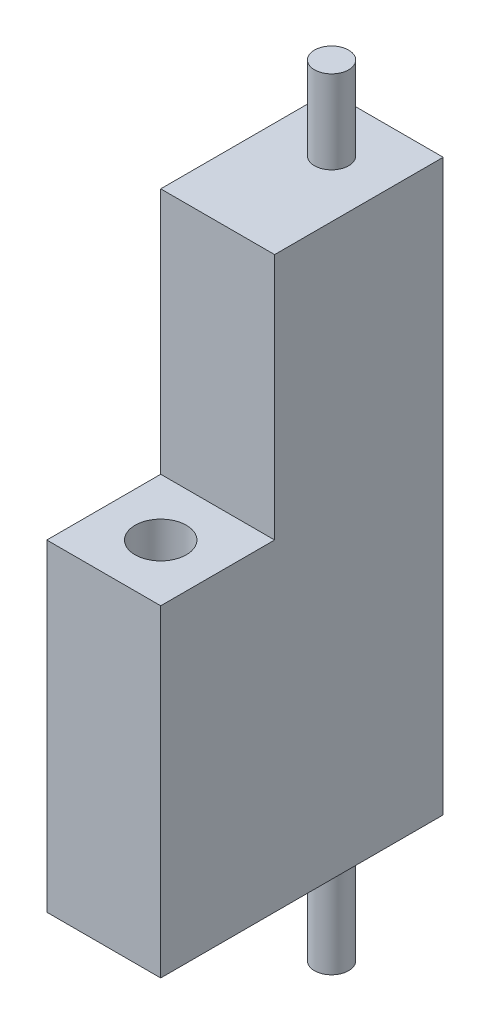
SolidWorks part; units mm, degrees
material "3003 合金"
ref_plane "前视基准面" through (0, 0, 0) normal (0, 0, 1) x (1, 0, 0)
ref_plane "上视基准面" through (0, 0, 0) normal (0, 1, 0) x (1, 0, 0)
ref_plane "右视基准面" through (0, 0, 0) normal (1, 0, 0) x (0, 0, -1)
sketch "草图1" plane through (0, 0, 0) normal (0, 0, 1) x (1, 0, 0)
  line L0 (22.5, 0) -> (22.5, 287.3668) construction
  line L1 (0, 0) -> (16.5, 0)
  line L2 (0, 0) -> (0, 10)
  line L3 (0, 10) -> (16.5, 10)
  line L4 (16.5, 0) -> (16.5, 10)
  line L5 (16.5, 0) -> (28.5, 0)
  line L6 (16.5, 0) -> (16.5, 10)
  line L7 (16.5, 10) -> (28.5, 10)
  line L8 (28.5, 0) -> (28.5, 10)
  line L9 (28.5, 10) -> (45, 10)
  line L10 (28.5, 10) -> (28.5, 0)
  line L11 (28.5, 0) -> (45, 0)
  line L12 (45, 10) -> (45, 0)
  line L13 (0, 10) -> (1, 10)
  line L14 (0, 10) -> (0, 102)
  line L15 (0, 102) -> (1, 102)
  line L16 (1, 10) -> (1, 102)
  line L17 (1, 102) -> (44, 102)
  line L18 (1, 102) -> (1, 10)
  line L19 (1, 10) -> (44, 10)
  line L20 (44, 102) -> (44, 10)
  line L21 (44, 102) -> (45, 102)
  line L22 (44, 102) -> (44, 10)
  line L23 (44, 10) -> (45, 10)
  line L24 (45, 102) -> (45, 10)
  line L25 (0, 0) -> (-10, 0)
  line L26 (0, 0) -> (0, 250)
  line L27 (0, 250) -> (-10, 250)
  line L28 (-10, 0) -> (-10, 250)
  line L29 (45, 0) -> (55, 0)
  line L30 (45, 0) -> (45, 250)
  line L31 (45, 250) -> (55, 250)
  line L32 (55, 0) -> (55, 250)
  line L33 (-10, 250) -> (55, 250)
  line L34 (-10, 250) -> (-10, 260)
  line L35 (-10, 260) -> (55, 260)
  line L36 (55, 260) -> (55, 250)
  line L37 (-10, 250) -> (55, 250)
  line L46 (-27.5, 0) -> (72.5, 0)
  line L47 (147.5, 475.7809) -> (197.5, 475.7809)
  line L52 (147.5, 475.7809) -> (172.5, 475.7809)
  line L56 (72.5, 0) -> (-27.5, 0)
  line L57 (72.5, 0) -> (72.5, 250)
  line L58 (72.5, 250) -> (-27.5, 250)
  line L59 (-27.5, 0) -> (-27.5, 250)
  line L60 (-27.5, 0) -> (72.5, 0)
  line L61 (-27.5, 0) -> (-27.5, -33)
  line L62 (-27.5, -33) -> (72.5, -33)
  line L63 (72.5, 250) -> (72.5, 0)
  line L64 (72.5, 0) -> (72.5, -33)
  point P21 (22.5, 0)
  dimension "D1" = 16.5
  dimension "D2" = 12
  dimension "D3" = 16.5
  dimension "D4" = 10
  dimension "D5" = 1
  dimension "D6" = 43
  dimension "D7" = 92
  dimension "D8" = 10
  dimension "D9" = 250
  dimension "D10" = 10
  dimension "D11" = 250
  dimension "D12" = 10
  dimension "D13" = 50
  dimension "D16" = 33
revolve "旋转1" add sketch "草图1" angle 360 about L0 region at (8.25, 5, 0) region at (-5, 125, 0) region at (0.5, 56, 0) region at (36.75, 5, 0) region at (50, 125, 0) region at (44.5, 56, 0)
sketch "草图3" plane through (0, 250, 0) normal (0, 1, 0) x (1, 0, 0)
  line L0 (-27.5, 0) -> (72.5, 0) construction
  line L1 (-27.5, 0) -> (22.5, 0)
  line L4 (22.5, 0) -> (22.5, 32.5)
  line L5 (72.5, 0) -> (-27.5, 0) construction
  line L6 (72.5, 0) -> (-27.5, 0) construction
  line L8 (22.5, 32.5) -> (22.5, 0)
  line L9 (22.5, 0) -> (72.5, 0)
  line L12 (22.5, 0) -> (72.5, 0)
  line L13 (22.5, 0) -> (22.5, -32.5)
  line L17 (22.5, -32.5) -> (22.5, 0)
  line L18 (22.5, 0) -> (-27.5, 0)
  line L20 (22.5, 0) -> (-27.5, 0)
  line L21 (22.5, 0) -> (22.5, 50)
  line L22 (22.5, 50) -> (-27.5, 50)
  line L23 (-27.5, 0) -> (-27.5, 50)
  line L24 (22.5, 0) -> (72.5, 0)
  line L25 (22.5, 0) -> (22.5, -50)
  line L26 (22.5, -50) -> (72.5, -50)
  line L27 (72.5, 0) -> (72.5, -50)
  line L28 (-27.5, 50) -> (72.5, 50)
  line L29 (-27.5, 50) -> (-27.5, -50)
  line L30 (-27.5, -50) -> (72.5, -50)
  line L31 (72.5, 50) -> (72.5, -50)
  circle A0 centre (22.5, 0) radius 32.5 construction
  circle A1 centre (22.5, 0) radius 32.5
  circle A2 centre (22.5, 0) radius 50
  circle M1 centre (22.5, 0) radius 32.5
  dimension "D1" = 100
  dimension "D5" = 50
extrude "凸台-拉伸1" add sketch "草图3" against normal blind 250 contours L23 L1 M1 | L1 M1 | L27 L9 M1 | L9 M1 region at (-4.1544, 250, -26.6544) region at (-4.1544, 250, 26.6544) region at (49.1544, 250, -26.6544) region at (49.1544, 250, 26.6544)
extrude "凸台-拉伸7" add sketch "草图3<5>" against normal blind 250 contours A2 L26 L27 | A2 L29 L30 | A2 L31 L28 | A2 L22 L23 region at (-16.3316, 250, 38.8316) region at (-16.3316, 250, -38.8316) region at (61.3316, 250, -38.8316) region at (61.3316, 250, 38.8316)
sketch "草图3<5>" plane through (0, 250, 0) normal (0, 1, 0) x (1, 0, 0) same geometry as "草图3"
extrude "凸台-拉伸8" add sketch "草图1<21>" along normal blind 50 and the other way blind 50 contours L64 L46 L29 L11 L5 L1 L25 L61 L62 region at (22.5, -16.5, 0)
sketch "草图1<21>" plane through (0, 0, 0) normal (0, 0, 1) x (1, 0, 0) same geometry as "草图1"
sketch "草图8" plane through (72.5, 0, 0) normal (1, 0, 0) x (0, 0, -1)
  line L0 (0, -33) -> (150, -33)
  line L1 (50, -33) -> (-50, -33) construction
  line L3 (150, -33) -> (135, -33)
  line L4 (150, -33) -> (150, 467)
  line L5 (150, 467) -> (135, 467)
  line L6 (135, -33) -> (135, 467)
  dimension "D1" = 150
  dimension "D2" = 15
  dimension "D3" = 500
sketch "草图9" plane through (0, 250, 0) normal (0, 1, 0) x (1, 0, 0)
sketch "草图10" plane through (0, 250, 0) normal (0, 1, 0) x (1, 0, 0)
  line L0 (72.5, 150) -> (72.5, 135) construction
  line L1 (22.5, 0) -> (72.5, 0) construction
  line L2 (22.5, 0) -> (22.5, 135) construction
  line L3 (22.5, 135) -> (72.5, 135) construction
  line L4 (72.5, 0) -> (72.5, 135) construction
sketch "草图12" plane through (0, 0, -50) normal (0, 0, -1) x (-1, 0, 0)
  line L0 (-72.5, -33) -> (-72.5, 467) construction
  line L1 (-72.5, 467) -> (27.5, 467)
  line L2 (-72.5, 467) -> (-72.5, -33)
  line L3 (-72.5, -33) -> (27.5, -33)
  line L4 (27.5, 467) -> (27.5, -33)
  line L5 (-72.5, -33) -> (-72.5, 467) construction
  line L6 (27.5, -33) -> (-72.5, -33) construction
  line L7 (27.5, -33) -> (27.5, 250) construction
extrude "凸台-拉伸10" add sketch "草图12" along normal blind 148
sketch "草图13" plane through (0, 467, 0) normal (0, 1, 0) x (1, 0, 0)
  line L0 (72.5, 150) -> (72.5, 135) construction
  line L1 (72.5, 150) -> (22.5, 150)
  line L2 (72.5, 150) -> (72.5, 135)
  line L3 (72.5, 135) -> (22.5, 135)
  line L4 (22.5, 150) -> (22.5, 135)
  circle A2 centre (22.5, 150) radius 15
extrude "凸台-拉伸12" add sketch "草图13" against normal blind 612 and the other way blind 73 contours L4 A2 L3 | L3 A2 L4 region at (28.8662, 467, -143.6338) region at (20.3779, 467, -152.1221)
sketch "草图15" plane through (0, 0, -198) normal (0, 0, -1) x (-1, 0, 0)
  line L0 (-72.5, -33) -> (-72.5, 467) construction
  line L1 (-22.5, 467) -> (-22.5, 578.0357)
  line L2 (27.5, 467) -> (-72.5, 467) construction
  line L3 (-22.5, 578.0357) -> (-22.5, 225.094)
  line L4 (-37.5, 467) -> (-72.5, 467)
  line L5 (-72.5, 467) -> (-72.5, 248.8087)
  line L6 (-7.5, 467) -> (27.5, 467)
  line L7 (27.5, 467) -> (27.5, 248.8087)
  spline S0 degree 3 poles (-37.5, 467) (-82.5811, 403.4849) (-64.3273, 320.5081) (-72.5, 248.8087) knots 0 0 0 0 1 1 1 1
  spline S1 degree 3 poles (-7.5, 467) (37.5811, 403.4849) (19.3273, 320.5081) (27.5, 248.8087) knots 0 0 0 0 1 1 1 1
sketch "草图14" plane through (72.5, 0, 0) normal (1, 0, 0) x (0, 0, -1)
  line L0 (198, 467) -> (198, -33) construction
  line L1 (198, 467) -> (50, 467) construction
  line L2 (50, 250) -> (50, 467)
  line L3 (50, 467) -> (135, 467)
  line L4 (164.1218, 467) -> (198, 467)
  line L5 (198, 467) -> (198, 250)
  spline S0 degree 3 poles (50, 250) (76.3156, 314.3966) (56.5596, 429.6801) (135, 467) knots 0 0 0 0 1 1 1 1
  spline S1 degree 2 poles (164.1218, 467) (193.0749, 360.4355) (198, 250) knots 0 0 0 1 1 1
  point P0 (135, 467)
  point P4 (198, 250)
  point P7 (164.1218, 467)
sketch "草图21" plane through (-27.5, 0, 0) normal (-1, 0, 0) x (0, 0, 1)
  line L0 (-50, 250) -> (-50, -33)
  line L1 (0, -33) -> (-150, -33) construction
sketch "草图20" plane through (0, -33, 0) normal (0, -1, 0) x (1, 0, 0)
  line L0 (-17.5, 40) -> (-17.5, 50)
  line L1 (-17.5, 40) -> (62.5, 40)
  line L2 (-17.5, 40) -> (-17.5, -188)
  line L3 (-17.5, -188) -> (62.5, -188)
  line L4 (62.5, 40) -> (62.5, -188)
  line L5 (-27.5, 50) -> (72.5, 50) construction
  line L6 (-17.5, 40) -> (-27.5, 40)
  line L7 (-27.5, -198) -> (-27.5, 50) construction
  line L8 (-27.5, -50) -> (72.5, -50)
  line L9 (72.5, 0) -> (72.5, -150) construction
  line L10 (-27.5, -50) -> (-27.5, -60)
  line L11 (-27.5, -60) -> (72.5, -60)
  circle M7 centre (22.5, -150) radius 15
  dimension "D1" = 228
  dimension "D2" = 80
  dimension "D3" = 10
  dimension "D4" = 10
  dimension "D5" = 10
extrude "切除-拉伸4" cut sketch "草图20" against normal blind 470 contours L8 L2 L3 L4 M7 region at (22.5, -33, -122.0722)
extrude "凸台-拉伸13" add sketch "草图20<4>" against normal blind 10 contours L11 L2 L3 L4 M7 region at (22.5, -33, -122.0722)
sketch "草图20<4>" plane through (0, -33, 0) normal (0, -1, 0) x (1, 0, 0) same geometry as "草图20"
sketch "草图22" plane through (0, -33, 0) normal (0, -1, 0) x (1, 0, 0)
  circle A0 centre (22.5, 0) radius 20.32
  dimension "D1" = 40.64
revolve "旋转2" add sketch "草图1<22>" angle 360 about L0 region at (19.5, 5, 0)
sketch "草图1<22>" plane through (0, 0, 0) normal (0, 0, 1) x (1, 0, 0) same geometry as "草图1"
extrude "切除-拉伸6" cut sketch "草图22" against normal blind 33
sketch "草图23" plane through (0, 0, 0) normal (0, -1, 0) x (1, 0, 0)
  circle A0 centre (22.5, 0) radius 17.5 construction
  circle A1 centre (22.5, 17.5) radius 2
  circle A2 centre (34.8744, 12.3744) radius 2
  circle A3 centre (40, 0) radius 2
  circle A4 centre (34.8744, -12.3744) radius 2
  circle A5 centre (22.5, -17.5) radius 2
  circle A6 centre (10.1256, -12.3744) radius 2
  circle A7 centre (5, 0) radius 2
  circle A8 centre (10.1256, 12.3744) radius 2
  circle A9 centre (22.5, 0) radius 14
  circle A10 centre (22.5, 0) radius 21
  circle A11 centre (22.5, 0) radius 8.75
  point P22 (22.5, 0)
  dimension "D1" = 35
  dimension "D2" = 4
  dimension "D4" = 28
  dimension "D5" = 42
  dimension "D6" = 17.5
  dimension "D3" = 8
extrude "切除-拉伸7" cut sketch "草图23" against normal blind 10 contours A4 | A3 | A2 | A1 | A8 | A7 | A6 | A5
sketch "草图25" plane through (0, 10, 0) normal (0, 1, 0) x (1, 0, 0)
  circle A0 centre (22.5, 0) radius 14
  dimension "D1" = 28
extrude "切除-拉伸8" cut sketch "草图25" against normal blind 3 contours A0
sketch "草图26" plane through (0, 10, 0) normal (0, 1, 0) x (1, 0, 0)
  circle A0 centre (22.5, 0) radius 8.75
  dimension "D1" = 17.5
extrude "切除-拉伸9" cut sketch "草图26" against normal blind 4 contours A0
sketch "草图27" plane through (0, 0, 0) normal (0, -1, 0) x (1, 0, 0)
  line L0 (28.5, 0) -> (30.5, 0) construction
  line L1 (22.5, 0) -> (72.5, 0) construction
  line L2 (30.5, -2) -> (30.5, 2) construction
  line L3 (30.5, -2) -> (30.5, 2) construction
  line L4 (30.5, 0) -> (25.0434, 0) construction
  line L5 (30.5, 2) -> (25.0434, 2) construction
  line L6 (25.0434, -2) -> (25.0434, 2) construction
  line L7 (30.5, -2) -> (25.0434, -2) construction
  line L8 (25.0434, 2) -> (30.5, 2) construction
  line L9 (25.0434, 2) -> (25.0434, -2) construction
  line L10 (30.5, 2) -> (30.5, -2)
  line L11 (25.0434, -2) -> (30.5, -2) construction
  line L12 (24.5, -8) -> (24.5, -2.5434)
  line L13 (20.5, -2.5434) -> (24.5, -2.5434)
  line L14 (20.5, -8) -> (24.5, -8)
  line L15 (20.5, -8) -> (20.5, -2.5434)
  line L24 (14.5, -2) -> (19.9566, -2) [skipped]
  line L25 (19.9566, 2) -> (19.9566, -2) [skipped]
  line L26 (14.5, 2) -> (19.9566, 2) [skipped]
  line L27 (14.5, 2) -> (14.5, -2) [skipped]
  line L28 (24.5, 2.5434) -> (20.5, 2.5434) [skipped]
  line L29 (24.5, 8) -> (24.5, 2.5434) [skipped]
  line L30 (20.5, 8) -> (20.5, 2.5434) [skipped]
  line L31 (24.5, 8) -> (20.5, 8) [skipped]
  circle A0 centre (22.5, 0) radius 6
  circle A1 centre (22.5, 0) radius 6
  circle A2 centre (22.5, 0) radius 6
  circle A3 centre (22.5, 0) radius 6
  point P30 (22.5, 0)
  dimension "D1" = 12
  dimension "D2" = 2
  dimension "D3" = 2
  dimension "D4" = 4
extrude "切除-拉伸10" cut sketch "草图27" against normal blind 6 contours A0
extrude "切除-拉伸12" cut sketch "草图27<5>" against normal blind 6 contours A0 L15 L14 L12 region at (22.5, 0, -6.941)
sketch "草图27<5>" plane through (0, 0, 0) normal (0, -1, 0) x (1, 0, 0) same geometry as "草图27"
